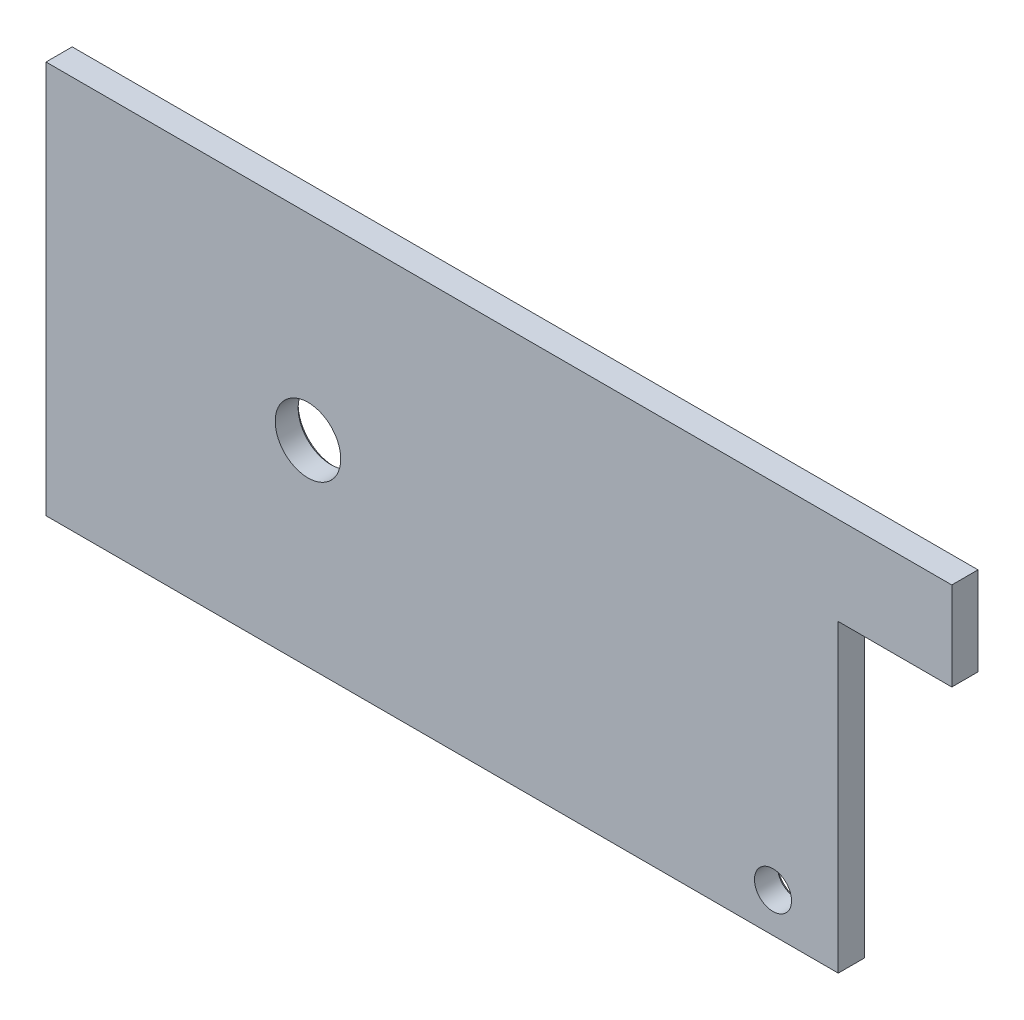
SolidWorks part; units mm, degrees
ref_plane "Front Plane" through (0, 0, 0) normal (0, 0, 1) x (1, 0, 0)
ref_plane "Top Plane" through (0, 0, 0) normal (0, 1, 0) x (1, 0, 0)
ref_plane "Right Plane" through (0, 0, 0) normal (1, 0, 0) x (0, 0, -1)
sketch "Sketch1" plane through (0, 0, 0) normal (0, 0, 1) x (1, 0, 0)
  line L1 (-81, -30) -> (39.9617, -30)
  line L6 (57.3, 16.5) -> (39.9617, 16.5)
  line L11 (57.3, 16.5) -> (57.3, 30)
  line L13 (39.9617, 16.5) -> (39.9617, -30)
  line L18 (57.3, 30) -> (-81, 30)
  line L19 (-81, 30) -> (-81, -30)
  circle A4 centre (-41, 0) radius 5
  circle A5 centre (30, -24) radius 2.83
  point P2 (-53.3757, 2.375)
  point P4 (-81, 0)
  point P7 (0, 0)
  point P9 (0, 0)
  point P10 (0, 0)
  point P11 (23, -24)
  dimension "D5" = 10
  dimension "D9" = 5.66
  dimension "D8" = 13.5
  dimension "D10" = 60
  dimension "D2" = 138.3
  dimension "D3" = 40
  dimension "D4" = 71
  dimension "D6" = 24
extrude "Boss-Extrude1" add sketch "Sketch1" along normal mid plane 4
chamfer "Chamfer1" distance 0.5 angle 45 2 edges at (32.83, -24, -2) (-36, 0, -2)
equation "\"back_boost\"= 7"
equation "\"D3@Sketch1\"=\"back_boost\"+33.00mm"
equation "\"D2@Sketch1\"=\"back_boost\"+131.30mm"
